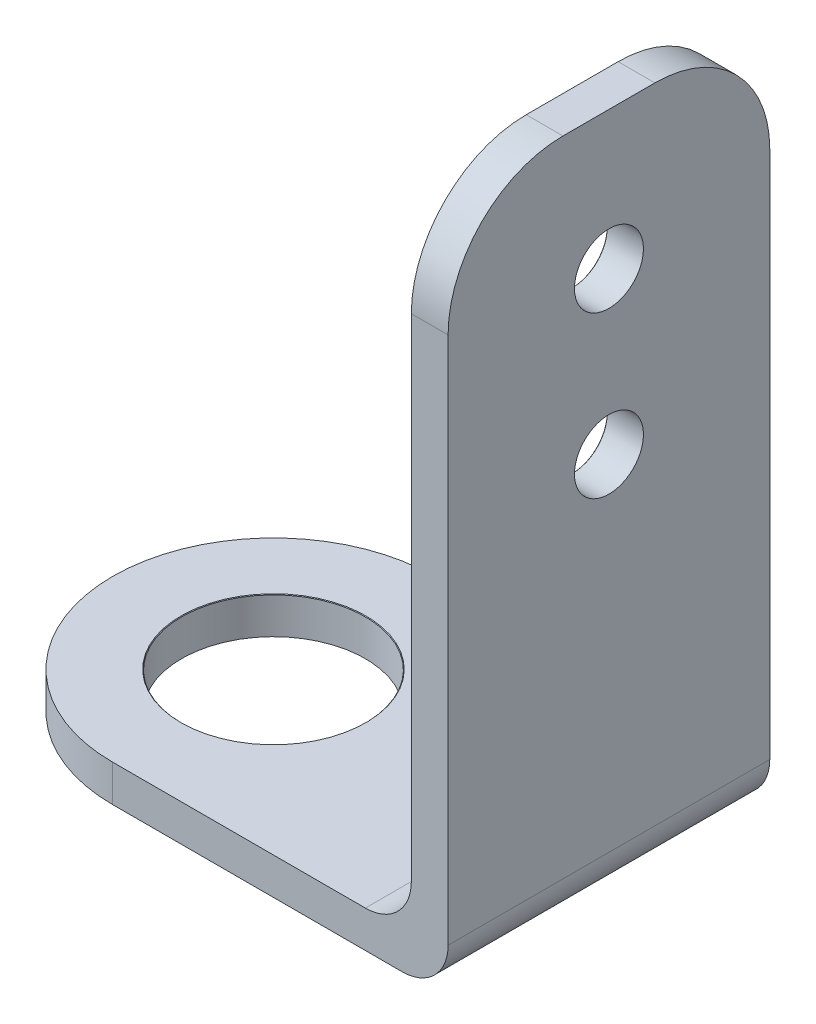
SolidWorks part; units mm, degrees
ref_plane "Front Plane" through (0, 0, 0) normal (0, 0, 1) x (1, 0, 0)
ref_plane "Top Plane" through (0, 0, 0) normal (0, 1, 0) x (1, 0, 0)
ref_plane "Right Plane" through (0, 0, 0) normal (1, 0, 0) x (0, 0, -1)
sketch "Sketch1" plane through (0, 0, 0) normal (0, 0, 1) x (1, 0, 0)
  line L0 (0, 0) -> (21.6, 0)
  line L1 (21.6, 0) -> (21.6, 30)
  line L2 (21.6, 30) -> (20, 30)
  line L3 (20, 30) -> (20, 1.6)
  line L4 (20, 1.6) -> (0, 1.6)
  line L5 (0, 1.6) -> (0, 0)
  dimension "D1" = 1.6
  dimension "D2" = 1.6
  dimension "D3" = 20
  dimension "D4" = 30
extrude "Boss-Extrude1" add sketch "Sketch1" along normal blind 14
fillet "Fillet1" 2 edges at (0, 0.8, 14) (0, 0.8, 0) type full round first side face at (13.8667, 10.5333, 14) second side face at (13.8667, 10.5333, 0) middle face at (0, 0.8, 7)
hole_wizard "Ø8.0mm Dowel Hole2" positions "Sketch5" profile "Sketch6" hole size "Ø8.0" standard "ISO"
sketch "Sketch5" plane through (0, 1.6, 0) normal (0, 1, 0) x (1, 0, 0)
  point P0 (7, -7)
sketch "Sketch6" plane through (7, 1.6, 7) normal (1, 0, 0) x (0, 0, 1)
  line L0 (0, 0) -> (0, 32.4034)
  line L1 (0, 32.4034) -> (4, 30)
  line L2 (4, 30) -> (4, 0.025)
  line L3 (4, 0.025) -> (4.025, 0)
  line L5 (4.025, 0) -> (0, 0)
  line L6 (-4, 0.025) -> (-4.025, 0) construction
  line L10 (0, 32.4034) -> (-4, 30) construction
  line L11 (0, -6.35) -> (0, 107.95) construction
  dimension "Hole Dia." = 8
  dimension "Hole Depth" = 30
  dimension "Near C'Sink Dia." = 8.05
  dimension "Near C'Sink Angle" = 90
  dimension "Drill Angle" = 118
hole_wizard "Ø3.0mm Dowel Hole1" positions "Sketch7" profile "Sketch8" hole size "Ø3.0" standard "ISO"
sketch "Sketch7" plane through (20, 0, 0) normal (-1, 0, 0) x (0, 0, 1)
  line L0 (14, 30) -> (14, 1.6) construction
  line L1 (14, 30) -> (0, 30) construction
  point P1 (7, 24)
  point P8 (7, 17)
  dimension "D1" = 7
  dimension "D2" = 6
  dimension "D3" = 7
sketch "Sketch8" plane through (20, 24, 7) normal (0, 1, 0) x (0, 0, 1)
  line L0 (0, 0) -> (0, 30.9013)
  line L1 (0, 30.9013) -> (1.5, 30)
  line L2 (1.5, 30) -> (1.5, 0.025)
  line L3 (1.5, 0.025) -> (1.525, 0)
  line L5 (1.525, 0) -> (0, 0)
  line L6 (-1.5, 0.025) -> (-1.525, 0) construction
  line L10 (0, 30.9013) -> (-1.5, 30) construction
  line L11 (0, -6.35) -> (0, 107.95) construction
  dimension "Hole Dia." = 3
  dimension "Hole Depth" = 30
  dimension "Near C'Sink Dia." = 3.05
  dimension "Near C'Sink Angle" = 90
  dimension "Drill Angle" = 118
fillet "Fillet2" radius 5 2 edges at (20.8, 30, 0) (20.8, 30, 14)
fillet "Fillet3" radius 2 2 edges at (20, 1.6, 7) (21.6, 0, 7)
